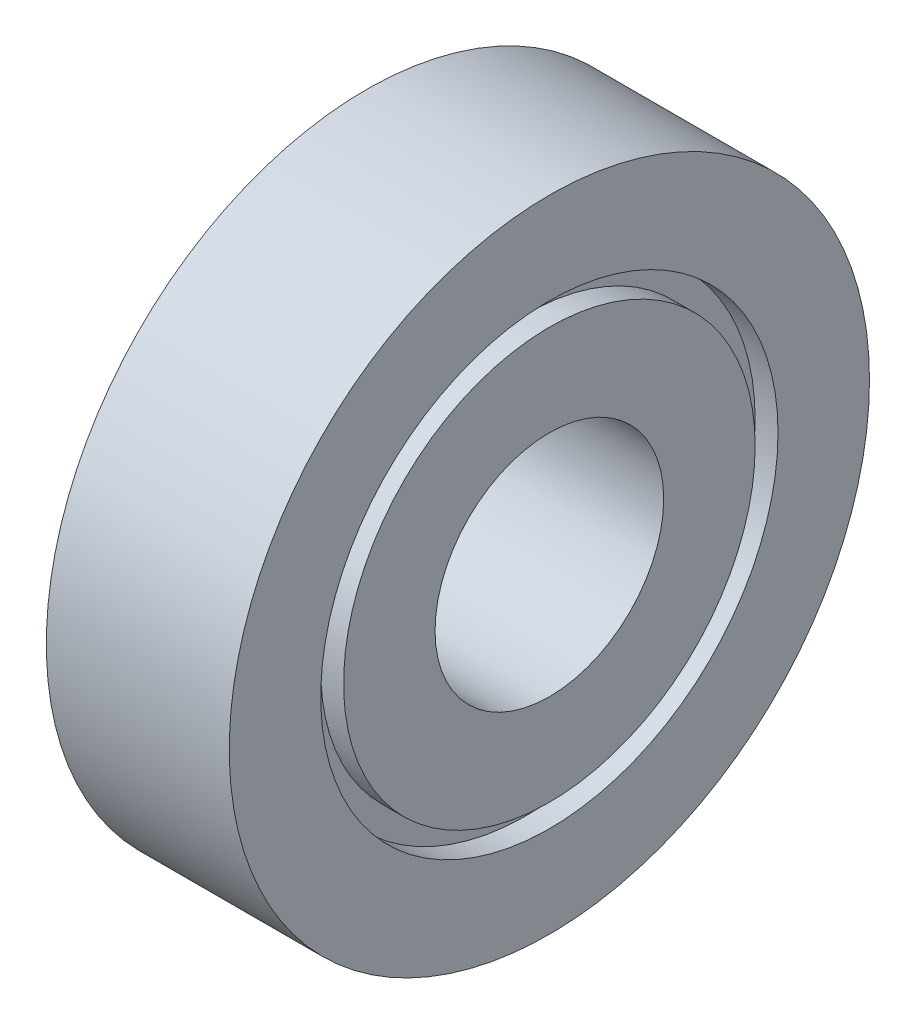
SolidWorks part; units mm, degrees
ref_plane "Front Plane" through (0, 0, 0) normal (0, 0, 1) x (1, 0, 0)
ref_plane "Top Plane" through (0, 0, 0) normal (0, 1, 0) x (1, 0, 0)
ref_plane "Right Plane" through (0, 0, 0) normal (1, 0, 0) x (0, 0, -1)
sketch "Sketch2" plane through (0, 0, 0) normal (1, 0, 0) x (0, 0, -1)
  circle A0 centre (0, 0) radius 7
  circle A1 centre (0, 0) radius 2.5
  circle A2 centre (0, 0) radius 4.5
  circle A3 centre (0, 0) radius 5
  dimension "D1" = 14
  dimension "D2" = 5
  dimension "D3" = 9
  dimension "D4" = 10
extrude "Boss-Extrude1" add sketch "Sketch2" along direction (1, 0, 0) on the side of the normal mid plane 4 contours A0 A3 region at (0, 0, 6.802)
extrude "Boss-Extrude2" add sketch "Sketch2<3>" along normal mid plane 3 contours A3 A2 region at (0, 0, 4.8586)
sketch "Sketch2<3>" plane through (0, 0, 0) normal (1, 0, 0) x (0, 0, -1) same geometry as "Sketch2"
extrude "Boss-Extrude3" add sketch "Sketch2<4>" along normal mid plane 4 contours A2 A1 region at (0, 0, 4.3727)
sketch "Sketch2<4>" plane through (0, 0, 0) normal (1, 0, 0) x (0, 0, -1) same geometry as "Sketch2"
